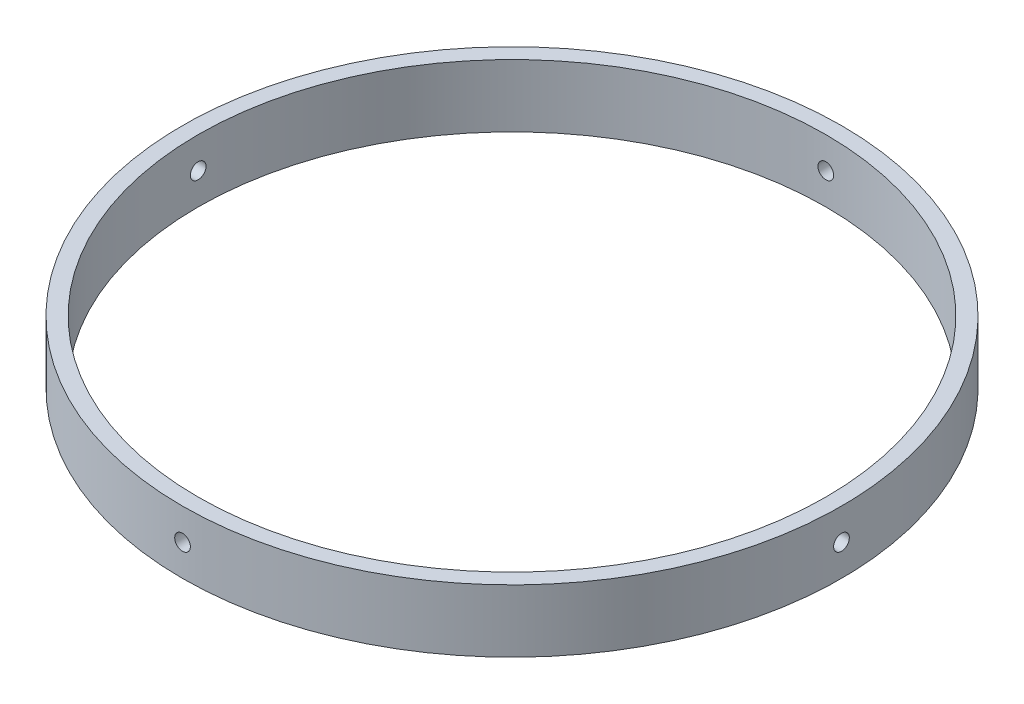
SolidWorks part; units mm, degrees
ref_plane "Front Plane" through (0, 0, 0) normal (0, 0, 1) x (1, 0, 0)
ref_plane "Top Plane" through (0, 0, 0) normal (0, 1, 0) x (1, 0, 0)
ref_plane "Right Plane" through (0, 0, 0) normal (1, 0, 0) x (0, 0, -1)
sketch "Sketch1" plane through (0, 0, 0) normal (0, 1, 0) x (1, 0, 0)
  circle A0 centre (0, 0) radius 66.802
  circle A1 centre (0, 0) radius 63.627
  dimension "D1" = 127.254
  dimension "D2" = 3.175
extrude "Boss-Extrude1" add sketch "Sketch1" along normal blind 12.7
sketch "Sketch2" plane through (0, 0, 0) normal (0, 0, 1) x (1, 0, 0)
  line L0 (0, 0) -> (0, 12.7) construction
  line L1 (63.627, 12.7) -> (-63.627, 12.7) construction
  circle A0 centre (0, 6.35) radius 1.5875
  point P7 (0, 6.35)
  dimension "D1" = 3.175
extrude "Cut-Extrude1" cut sketch "Sketch2" against normal up to surface (66.7831 mm away) up to face at (0, 12.7, 66.802)
pattern_circular "CirPattern1" count 4 over 360 about axis through (0, 12.7, 0) along (0, -1, 0) of "Cut-Extrude1" reverse direction yes
